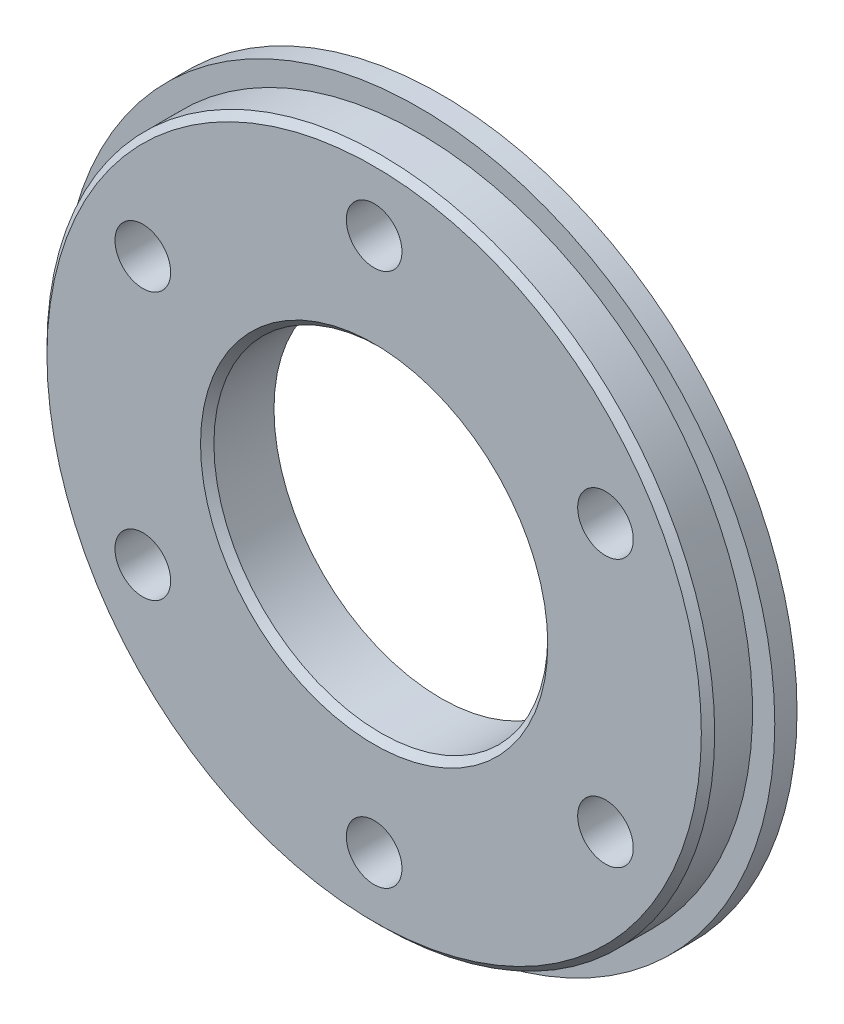
SolidWorks part; units mm, degrees
material "6061 合金"
ref_plane "前视基准面" through (0, 0, 0) normal (0, 0, 1) x (1, 0, 0)
ref_plane "上视基准面" through (0, 0, 0) normal (0, 1, 0) x (1, 0, 0)
ref_plane "右视基准面" through (0, 0, 0) normal (1, 0, 0) x (0, 0, -1)
other "Configuration Table"
sketch "草图1" plane through (0, 0, 0) normal (0, 0, 1) x (1, 0, 0)
  circle A1 centre (0, 0) radius 15
  dimension "D2" = 30
extrude "凸台-拉伸5" add sketch "草图1" along normal blind 3
sketch "草图8" plane through (0, 0, 0) normal (0, 0, -1) x (-1, 0, 0)
  circle A0 centre (0, 0) radius 16
  dimension "D1" = 32
extrude "凸台-拉伸7" add sketch "草图8" against normal blind 1
sketch "草图9" plane through (0, 0, 0) normal (0, 0, -1) x (-1, 0, 0)
  circle A0 centre (0, 0) radius 7.5
  dimension "D1" = 15
extrude "切除-拉伸3" cut sketch "草图9" against normal blind 9 contours A0
sketch "草图10" plane through (0, 0, 0) normal (0, 0, -1) x (-1, 0, 0)
  circle A0 centre (0, 0) radius 12 construction
  circle A1 centre (0, 12) radius 1.25
  circle A2 centre (10.3923, 6) radius 1.25
  circle A3 centre (10.3923, -6) radius 1.25
  circle A4 centre (0, -12) radius 1.25
  circle A5 centre (-10.3923, -6) radius 1.25
  circle A6 centre (-10.3923, 6) radius 1.25
  point P3 (0, 12)
  point P5 (10.3923, 6)
  point P9 (10.3923, -6)
  point P11 (0, -12)
  point P13 (-10.3923, -6)
  point P15 (-10.3923, 6)
  point P17 (0, 0)
  dimension "D1" = 24
  dimension "D2" = 2.5
  dimension "D3" = 6
hole_wizard "M3 螺纹孔1" positions "草图10" profile "草图11" tap size "M3" standard "GB" end condition through all
sketch "草图11" plane through (0, 0, 0) normal (1, 0, 0) x (0, 1, 0)
  line L0 (0, 0) -> (0, 3)
  line L1 (0, 3) -> (1.25, 3)
  line L2 (1.25, 3) -> (1.25, 0)
  line L5 (1.25, 0) -> (0, 0)
  line L11 (0, -6.35) -> (0, 107.95) construction
  dimension "通孔螺纹孔钻头直径" = 2.5
  dimension "通孔螺纹孔钻头深度" = 3
cosmetic thread "孔螺蚊线1"
cosmetic thread "孔螺蚊线2"
cosmetic thread "孔螺蚊线3"
cosmetic thread "孔螺蚊线4"
cosmetic thread "孔螺蚊线5"
cosmetic thread "孔螺蚊线6"
chamfer "倒角1" distance 0.3 angle 45 1 edges at (15, 0, 3)
chamfer "倒角2" distance 0.3 angle 45 1 edges at (7.5, 0, 3)
